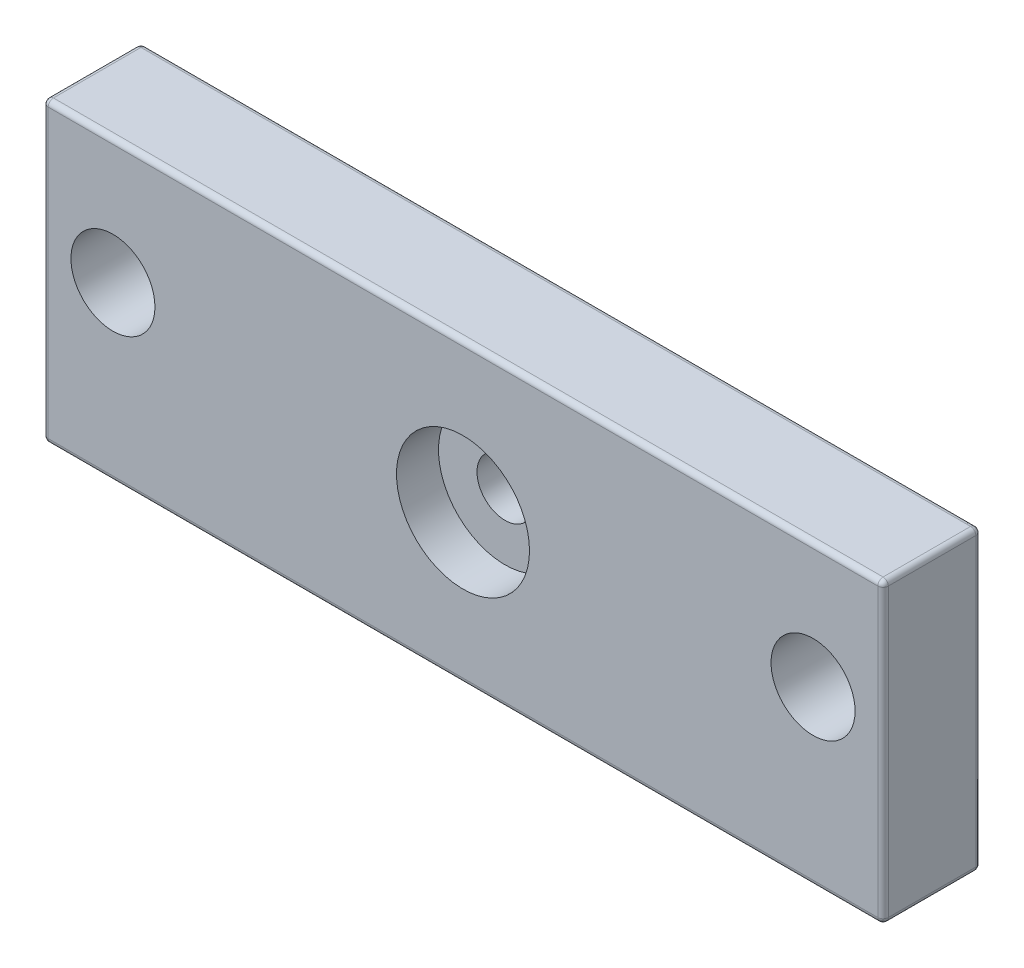
SolidWorks part; units mm, degrees
ref_plane "Front Plane" through (0, 0, 0) normal (0, 0, 1) x (1, 0, 0)
ref_plane "Top Plane" through (0, 0, 0) normal (0, 1, 0) x (1, 0, 0)
ref_plane "Right Plane" through (0, 0, 0) normal (1, 0, 0) x (0, 0, -1)
sketch "Sketch1" plane through (0, 0, 0) normal (0, 0, 1) x (1, 0, 0)
  line L1 (-60, -21.25) -> (60, -21.25)
  line L2 (-60, -21.25) -> (-60, 21.25)
  line L3 (-60, 21.25) -> (60, 21.25)
  line L4 (60, -21.25) -> (60, 21.25)
  line L5 (-60, -21.25) -> (60, 21.25) construction
  line L6 (-60, 21.25) -> (60, -21.25) construction
  point P0 (0, 0)
  dimension "D1" = 120
  dimension "D2" = 42.5
extrude "Boss-Extrude1" add sketch "Sketch1" along normal mid plane 14
sketch "Sketch2" plane through (0, 0, 7) normal (0, 0, 1) x (1, 0, 0)
  circle A0 centre (0, 0) radius 9.5
  dimension "D1" = 19
extrude "Cut-Extrude1" cut sketch "Sketch2" against normal blind 6
sketch "Sketch3" plane through (0, 0, 1) normal (0, 0, 1) x (1, 0, 0)
  circle A0 centre (0, 0) radius 4
  dimension "D1" = 8
extrude "Cut-Extrude2" cut sketch "Sketch3" against normal through all
sketch "Sketch5" plane through (0, 0, 7) normal (0, 0, 1) x (1, 0, 0)
  line L0 (-40.6477, 3.4) -> (36.4799, 3.4) construction
  circle A0 centre (-50, 3.4) radius 6
  circle A1 centre (50, 3.4) radius 6
  dimension "D1" = 12
  dimension "D2" = 12
  dimension "D4" = 50
  dimension "D3" = 50
  dimension "D5" = 3.4
extrude "Cut-Extrude4" cut sketch "Sketch5" against normal through all
sketch "Sketch6" plane through (0, -21.25, 0) normal (0, -1, 0) x (1, 0, 0)
  line L0 (-60, 0) -> (60, 0) construction
  line L1 (-60, 7) -> (-60, -7) construction
  line L2 (60, 7) -> (60, -7) construction
  circle A0 centre (-50, 0) radius 2.1
  circle A1 centre (-25, 0) radius 2.1
  circle A2 centre (25, 0) radius 2.1
  circle A3 centre (50, 0) radius 2.1
  circle A4 centre (-37.5, 0) radius 1.25
  circle A5 centre (37.5, 0) radius 1.25
  dimension "D1" = 4.2
  dimension "D2" = 4.2
  dimension "D3" = 4.2
  dimension "D4" = 4.2
  dimension "D5" = 10
  dimension "D9" = 2.5
  dimension "D10" = 2.5
  dimension "D11" = 22.5
  dimension "D12" = 22.5
  dimension "D6" = 35
  dimension "D7" = 10
  dimension "D8" = 35
extrude "Cut-Extrude5" cut sketch "Sketch6" against normal blind 10
fillet "Fillet1" radius 0.75 12 edges at (60, 21.25, 0) (60, 0, -7) (0, 21.25, -7) (60, 0, 7) (60, -21.25, 0) (0, -21.25, -7) (0, 21.25, 7) (-60, 21.25, 0) (-60, 0, -7) (0, -21.25, 7) (-60, -21.25, 0) (-60, 0, 7)
